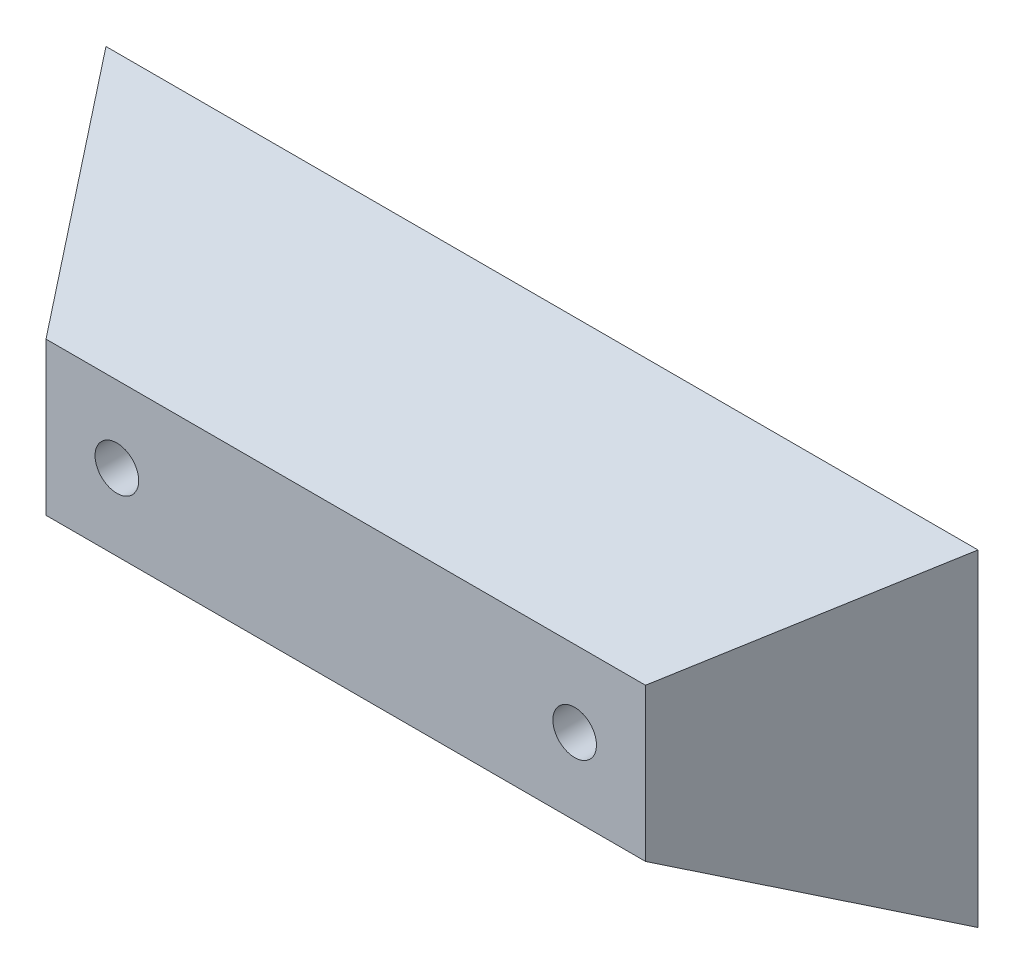
SolidWorks part; units mm, degrees
ref_plane "Płaszczyzna przednia" through (0, 0, 0) normal (0, 0, 1) x (1, 0, 0)
ref_plane "Płaszczyzna górna" through (0, 0, 0) normal (0, 1, 0) x (1, 0, 0)
ref_plane "Płaszczyzna prawa" through (0, 0, 0) normal (1, 0, 0) x (0, 0, -1)
sketch "Szkic1" plane through (0, 0, 0) normal (0, 1, 0) x (1, 0, 0)
  line L0 (-40, 0) -> (-27.5, -18)
  line L1 (-27.5, -18) -> (27.5, -18)
  line L2 (27.5, -18) -> (40, 0)
  line L3 (40, 0) -> (-40, 0)
  point P2 (0, 0)
  point P5 (0, 0)
  point P6 (0, 0)
  point P7 (0, 0)
  point P8 (0, 0)
extrude "Dodanie-wyciągnięcie1" add sketch "Szkic1" along normal blind 30
sketch "Szkic2" plane through (0, 0, 0) normal (0, 0, -1) x (-1, 0, 0)
  circle A0 centre (-21, 15) radius 2
  circle A1 centre (21, 15) radius 2
  point P4 (0, 0)
  point P5 (0, 0)
extrude "Wytnij-wyciągnięcie1" cut sketch "Szkic2" against normal up to next
chamfer "Sfazowanie1" distance 18 distance2 8 1 edges at (0, 0, 18) first distance on face at (0, 0, 9)
chamfer "Sfazowanie2" distance 8 distance2 18 1 edges at (0, 30, 18) first distance on face at (19, 15, 18)
